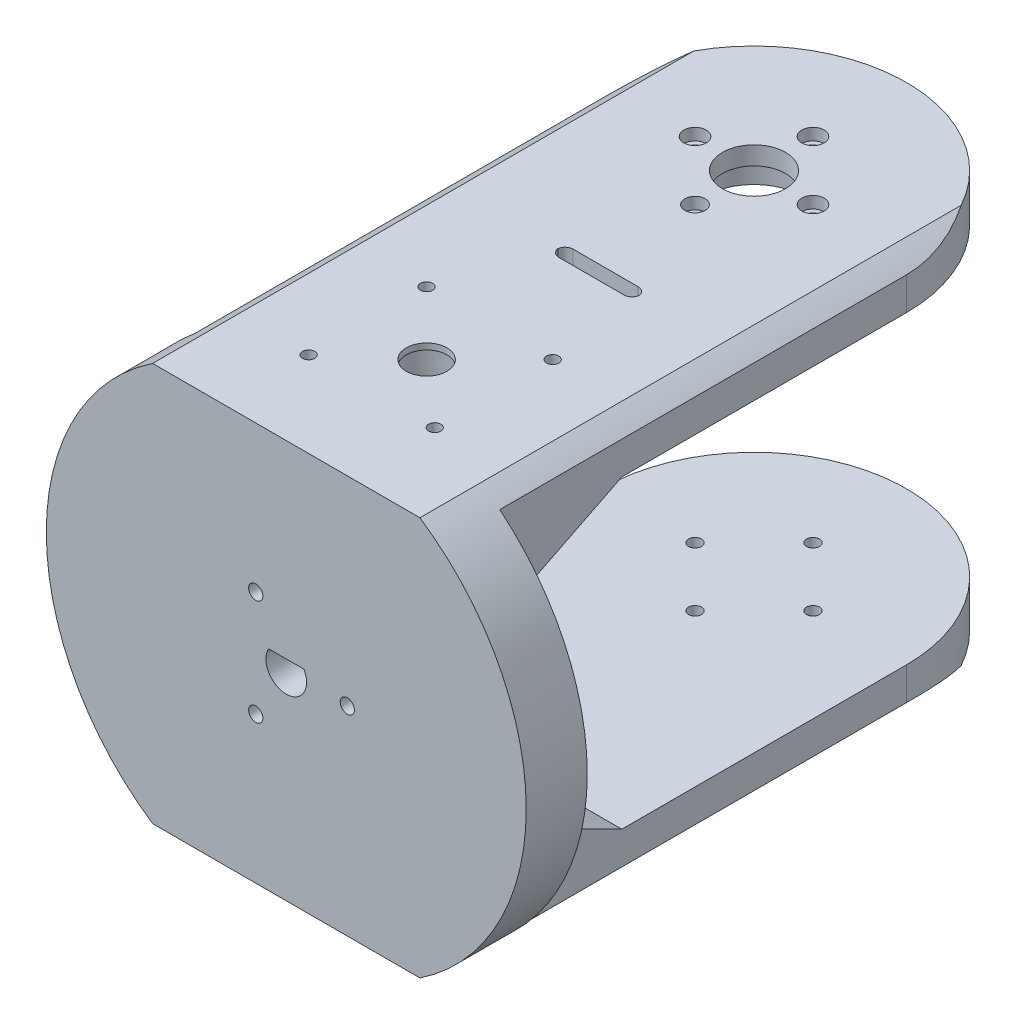
SolidWorks part; units mm, degrees
material "Custom Plastic"
ref_plane "Front Plane" through (0, 0, 0) normal (0, 0, 1) x (1, 0, 0)
ref_plane "Top Plane" through (0, 0, 0) normal (0, 1, 0) x (1, 0, 0)
ref_plane "Right Plane" through (0, 0, 0) normal (1, 0, 0) x (0, 0, -1)
sketch "Sketch1" plane through (0, 0, 0) normal (0, 0, 1) x (1, 0, 0)
  line L0 (0, 0) -> (-4.3301, 2.5) construction
  line L1 (0, 0) -> (-5, 0) construction
  line L2 (-4.3301, 2.5) -> (4.3301, 2.5)
  circle A0 centre (0, 0) radius 59
  arc A1 (-4.3301, 2.5) -> (4.3301, 2.5) centre (0, 0) ccw
  dimension "D1" = 118
  dimension "D2" = 10
  dimension "D3" = 30
extrude "Base" add sketch "Sketch1" along normal blind 15
sketch "Sketch2" plane through (0, 0, 0) normal (0, 0, -1) x (-1, 0, 0)
  circle A0 centre (0, 0) radius 20
  dimension "D1" = 40
extrude "TopGrove" cut sketch "Sketch2" against normal blind 2
sketch "Sketch4" plane through (0, 0, 0) normal (0, 0, -1) x (-1, 0, 0)
  line L2 (0, 0) -> (0, -65) construction
  line L6 (-20, 0) -> (20, 0) construction
  line L9 (-37.5, 37.5) -> (37.5, 37.5)
  line L10 (37.5, 37.5) -> (37.5, 45.5494)
  line L11 (-37.5, 37.5) -> (-37.5, 45.5494)
  line L12 (0, 0) -> (0, 59) construction
  line L13 (-37.5, -37.5) -> (-37.5, -45.5494)
  line L14 (37.5, -37.5) -> (37.5, -45.5494)
  line L15 (-37.5, -37.5) -> (37.5, -37.5)
  arc A1 (41.7193, -41.7193) -> (-41.7193, -41.7193) centre (0, 0) ccw construction
  arc A4 (-37.5, 45.5494) -> (37.5, 45.5494) centre (0, 0) cw
  circle A5 centre (0, 0) radius 20 construction
  circle A6 centre (0, 0) radius 20 construction
  arc A7 (-37.5, -45.5494) -> (37.5, -45.5494) centre (0, 0) ccw
  point P22 (0, 37.5)
  dimension "D1" = 118
  dimension "D3" = 37.5
  dimension "D2" = 75
extrude "Boss-Extrude3" add sketch "Sketch4" along normal blind 100
sketch "Sketch3" plane through (0, 0, 2) normal (0, 0, -1) x (-1, 0, 0)
  line L0 (0, 0) -> (-15, 0) construction
  circle A0 centre (0, 0) radius 15 construction
  circle A1 centre (-15, 0) radius 1.75
  circle A5 centre (7.5, 12.9904) radius 1.75
  circle A6 centre (7.5, -12.9904) radius 1.75
  circle A7 centre (0, 0) radius 5 construction
  point P12 (0, 0)
  point P14 (0, 0)
  dimension "D1" = 30
  dimension "D2" = 3.5
  dimension "D3" = 3
extrude "Cut-Extrude2" cut sketch "Sketch3" against normal up to surface (13 mm away) up to face at (59, 0, 15)
sketch "Sketch6" plane through (0, -37.5, 0) normal (0, 1, 0) x (1, 0, 0)
  line L0 (37.5, 100) -> (-37.5, 100) construction
  line L1 (37.5, 100) -> (-37.5, 100)
  arc A0 (37.5, 100) -> (-37.5, 100) centre (0, 100) ccw
extrude "Boss-Extrude4" add sketch "Sketch6" against normal up to surface (8.0494 mm away) up to face at (59, 0, 15)
sketch "Sketch7" plane through (0, 37.5, 0) normal (0, -1, 0) x (1, 0, 0)
  line L0 (37.5, -100) -> (-37.5, -100)
  arc A0 (-37.5, -100) -> (37.5, -100) centre (0, -100) ccw
extrude "Boss-Extrude5" add sketch "Sketch7" against normal up to surface (8.0494 mm away) up to face at (59, 0, 15)
ref_plane "Plane1" through (0, 37.5, 0) normal (0, -1, 0) x (-1, 0, 0)
sketch "Sketch8" plane through (0, 37.5, 0) normal (0, -1, 0) x (-1, 0, 0)
  line L0 (59, 0) -> (37.5, 0) construction
  line L1 (59, 0) -> (37.5, 0) construction
  line L2 (37.5, 0) -> (-37.5, 0) construction
  line L3 (0, 0) -> (0, 137.5) construction
  line L5 (15.5, 6) -> (-15.5, 6) construction
  line L6 (15.5, 6) -> (15.5, 35) construction
  line L7 (15.5, 35) -> (-15.5, 35) construction
  line L8 (-15.5, 6) -> (-15.5, 35) construction
  arc A0 (37.5, 100) -> (-37.5, 100) centre (0, 100) ccw construction
  circle A1 centre (0, 19.5) radius 5
  circle A2 centre (15.5, 35) radius 1.5
  circle A3 centre (-15.5, 35) radius 1.5
  circle A4 centre (-15.5, 6) radius 1.5
  circle A5 centre (15.5, 6) radius 1.5
  circle A6 centre (0, 100) radius 7.75
  arc A7 (37.5, 100) -> (-37.5, 100) centre (0, 100) ccw construction
  dimension "D1" = 15.5
  dimension "D4" = 3
  dimension "D5" = 10
  dimension "D8" = 15.5
  dimension "D2" = 6
  dimension "D3" = 19.5
  dimension "D6" = 15.5
  dimension "D7" = 15.5
extrude "Cut-Extrude3" cut sketch "Sketch8" against normal up to next
sketch "Sketch9" plane through (0, 37.5, 0) normal (0, -1, 0) x (1, 0, 0)
  circle A0 centre (0, -19.5) radius 8.5
  dimension "D1" = 17
extrude "Cut-Extrude4" cut sketch "Sketch9" against normal blind 10
ref_plane "Plane2" through (-47.5, 0, 0) normal (-1, 0, 0) x (0, 0, 1)
sketch "Sketch10" plane through (-47.5, 0, 0) normal (-1, 0, 0) x (0, 0, 1)
  line L0 (-100, 45.5494) -> (0, 45.5494) construction
  line L1 (-24.5, 59) -> (-92.25, 59) construction
  line L2 (-147.739, 45.5494) -> (14.8431, 45.5494) construction
  line L3 (16.5, 59) -> (-145.875, 59) construction
  line L4 (0, 49) -> (0, 59)
  line L5 (-137.5, 59) -> (0, 59)
  line L6 (-137.5, 59) -> (-137.5, 37.5) construction
  line L7 (-137.5, 59) -> (-137.5, 49)
  line L8 (-137.5, 49) -> (0, 49)
  dimension "D1" = 10
extrude "Cut-Extrude5" cut sketch "Sketch10" against normal through all both and the other way through all
ref_plane "Plane3" through (0, 77.5, 0) normal (0, -1, 0) x (-1, 0, 0)
sketch "Sketch11" plane through (0, 77.5, 0) normal (0, -1, 0) x (-1, 0, 0)
  line L0 (-37.5, 100) -> (-37.5, 0) construction
  line L1 (37.5, 100) -> (37.5, 0) construction
  line L2 (-37.5, 100) -> (-37.5, 0)
  line L3 (37.5, 100) -> (37.5, 0)
  line L4 (37.5, 0) -> (-37.5, 0)
  arc A0 (-32.8634, 118.0624) -> (-37.5, 100) centre (0, 100) ccw construction
  arc A1 (32.8634, 118.0624) -> (-32.8634, 118.0624) centre (0, 100) ccw construction
  arc A2 (37.5, 100) -> (32.8634, 118.0624) centre (0, 100) ccw construction
  arc A3 (-32.8634, 118.0624) -> (-37.5, 100) centre (0, 100) ccw
  arc A4 (32.8634, 118.0624) -> (-32.8634, 118.0624) centre (0, 100) ccw
  arc A5 (37.5, 100) -> (32.8634, 118.0624) centre (0, 100) ccw
sketch "Sketch12" plane through (0, 0, 0) normal (0, 0, -1) x (-1, 0, 0)
  line L1 (-32.8634, 49) -> (32.8634, 49)
  line L2 (-32.8634, 49) -> (32.8634, 49)
  arc A1 (32.8634, 49) -> (-32.8634, 49) centre (0, 0) ccw
  arc A2 (32.8634, 49) -> (-32.8634, 49) centre (0, 0) ccw
  dimension "D1" = 0
extrude "Cut-Extrude6" cut sketch "Sketch12" against normal through all
sketch "Sketch13" plane through (0, -37.5, 0) normal (0, 1, 0) x (1, 0, 0)
  circle A0 centre (0, 100) radius 14.5 construction
  circle A1 centre (0, 114.5) radius 1.6
  circle A2 centre (0, 100) radius 14.5 construction
  circle A3 centre (14.5, 100) radius 1.6
  circle A4 centre (0, 100) radius 14.5 construction
  circle A5 centre (0, 85.5) radius 1.6
  circle A6 centre (0, 100) radius 14.5 construction
  circle A7 centre (-14.5, 100) radius 1.6
  dimension "D1" = 29
  dimension "D2" = 3.2
  dimension "D3" = 4
extrude "Cut-Extrude7" cut sketch "Sketch13" against normal through all both and the other way through all
sketch "Sketch14" plane through (-47.5, 0, 0) normal (-1, 0, 0) x (0, 0, 1)
  line L0 (-100, -37.5) -> (0, -37.5) construction
  line L1 (-150, -49) -> (25, -49)
  line L2 (-150, -49) -> (-150, -124)
  line L3 (-150, -124) -> (25, -124)
  line L4 (25, -49) -> (25, -124)
  line L5 (15, -59) -> (15, 49) construction
  dimension "D1" = 11.5
  dimension "D2" = 10
  dimension "D3" = 175
  dimension "D4" = 75
extrude "Cut-Extrude8" cut sketch "Sketch14" against normal through all
sketch "Sketch15" plane through (0, 37.5, 0) normal (0, -1, 0) x (1, 0, 0)
  circle A0 centre (0, -100) radius 12.05
  dimension "D1" = 24.1
extrude "Cut-Extrude9" cut sketch "Sketch15" against normal blind 7
sketch "Sketch16" plane through (0, 49, 0) normal (0, 1, 0) x (1, 0, 0)
  line L0 (0, 100) -> (0, 19.5) construction
  line L2 (-7.5, 61.0229) -> (12.5, 61.0229)
  line L3 (-7.5, 61.0229) -> (-7.5, 57.5229)
  line L4 (-7.5, 57.5229) -> (12.5, 57.5229)
  line L5 (12.5, 61.0229) -> (12.5, 57.5229)
  dimension "D1" = 20
  dimension "D2" = 3.5
  dimension "D3" = 7.5
sketch "Sketch23" plane through (0, 49, 0) normal (0, 1, 0) x (1, 0, 0)
  circle A0 centre (0, 114.5) radius 2.75
  circle A1 centre (-14.5, 100) radius 2.75
  circle A2 centre (14.5, 100) radius 2.75
  circle A3 centre (0, 85.5) radius 2.5
  dimension "D1" = 5.5
  dimension "D2" = 5.5
  dimension "D3" = 5.5
  dimension "D4" = 5
extrude "Cut-Extrude15" cut sketch "Sketch23" against normal blind 2.9
extrude "Cut-Extrude10" cut sketch "Sketch16" against normal up to surface (11.5 mm away) up to face at (0, 37.5, -112.05)
fillet "Fillet4" radius 2 4 edges at (12.5, 43.25, -61.0229) (12.5, 43.25, -57.5229) (-7.5, 43.25, -57.5229) (-7.5, 43.25, -61.0229)
sketch "Sketch17" plane through (0, 0, 2) normal (0, 0, -1) x (-1, 0, 0)
  circle A0 centre (7.5, 12.9904) radius 3.5
  circle A1 centre (7.5, -12.9904) radius 3.5
  circle A2 centre (-15, 0) radius 3.5
  dimension "D1" = 7
  dimension "D2" = 7
  dimension "D3" = 7
extrude "Cut-Extrude11" cut sketch "Sketch17" against normal blind 4
sketch "Sketch18" plane through (0, -49, 0) normal (0, -1, 0) x (1, 0, 0)
  circle A0 centre (0, -114.5) radius 3
  circle A1 centre (0, -85.5) radius 3
  circle A2 centre (-14.5, -100) radius 3
  circle A3 centre (14.5, -100) radius 3
  dimension "D1" = 6
  dimension "D2" = 6
  dimension "D3" = 6
  dimension "D4" = 6
extrude "Cut-Extrude12" cut sketch "Sketch18" against normal blind 3
sketch "Sketch19" plane through (0, 0, 0) normal (0, 0, -1) x (-1, 0, 0)
  line L0 (-37.5, 37.5) -> (37.5, 37.5) construction
  line L1 (22.5, 37.5) -> (-22.5, 37.5)
  line L2 (22.5, 37.5) -> (22.5, -22.5)
  line L3 (22.5, -22.5) -> (-22.5, -22.5)
  line L4 (-22.5, 37.5) -> (-22.5, -22.5)
  line L5 (-37.5, 45.5494) -> (-37.5, 37.5) construction
  dimension "D1" = 15
  dimension "D2" = 15
  dimension "D3" = 60
extrude "Cut-Extrude13" cut sketch "Sketch19" against normal blind 2
sketch "Sketch20" plane through (37.5, 0, 0) normal (1, 0, 0) x (0, 0, -1)
  line L0 (0, -45.5494) -> (0, 45.5494) construction
  line L1 (100, -37.5) -> (0, -37.5) construction
  line L2 (0, -45.5494) -> (0, 45.5494) construction
  line L3 (100, -37.5) -> (0, -37.5) construction
  line L4 (30, -37.5) -> (0, -37.5)
  line L5 (0, -37.5) -> (0, -22.5)
  line L6 (0, -22.5) -> (30, -37.5)
  dimension "D1" = 15
  dimension "D2" = 30
extrude "Boss-Extrude6" add sketch "Sketch20" against normal blind 10
ref_plane "Plane4" through (37.5, 0, 0) normal (1, 0, 0) x (0, 0, -1)
mirror "Mirror1" about plane through (0, 0, 0) normal (1, 0, 0) of "Boss-Extrude6"
fillet "Fillet5" radius 5 1 edges at (0, -37.5, 0)
fillet "Fillet6" radius 5 2 edges at (30, 37.5, 0) (-30, 37.5, 0)
sketch "Sketch21" plane through (0, 37.5, 0) normal (0, -1, 0) x (1, 0, 0)
  line L0 (10.5, -57.5229) -> (-5.5, -57.5229) construction
  line L1 (-5.5, -61.0229) -> (10.5, -61.0229) construction
  line L2 (10.5, -57.5229) -> (-5.5, -57.5229) construction
  line L3 (-5.5, -61.0229) -> (10.5, -61.0229) construction
  line L4 (10.5, -54.5229) -> (-5.5, -54.5229)
  line L5 (-5.5, -64.0229) -> (10.5, -64.0229)
  arc A0 (-7.4843, -59.2729) -> (-5.5, -61.0229) centre (-5.5, -59.0229) ccw construction
  arc A1 (-5.5, -57.5229) -> (-7.4843, -59.2729) centre (-5.5, -59.5229) ccw construction
  arc A2 (10.5, -61.0229) -> (12.4843, -59.2729) centre (10.5, -59.0229) ccw construction
  arc A3 (12.4843, -59.2729) -> (10.5, -57.5229) centre (10.5, -59.5229) ccw construction
  arc A4 (-7.4843, -59.2729) -> (-5.5, -61.0229) centre (-5.5, -59.0229) ccw construction
  arc A5 (-5.5, -57.5229) -> (-7.4843, -59.2729) centre (-5.5, -59.5229) ccw construction
  arc A6 (10.5, -61.0229) -> (12.4843, -59.2729) centre (10.5, -59.0229) ccw construction
  arc A7 (12.4843, -59.2729) -> (10.5, -57.5229) centre (10.5, -59.5229) ccw construction
  arc A8 (-5.5, -54.5229) -> (-10.4937, -59.2729) centre (-5.5, -59.5229) ccw
  arc A9 (-10.4937, -59.2729) -> (-5.5, -64.0229) centre (-5.5, -59.0229) ccw
  arc A10 (10.5, -64.0229) -> (15.4937, -59.2729) centre (10.5, -59.0229) ccw
  arc A11 (15.4937, -59.2729) -> (10.5, -54.5229) centre (10.5, -59.5229) ccw
  dimension "D1" = 3
extrude "Cut-Extrude14" cut sketch "Sketch21" against normal blind 3.5
mirror "Mirror2" about plane through (0, 0, 0) normal (0, 1, 0) of "Mirror1", "Boss-Extrude6"
